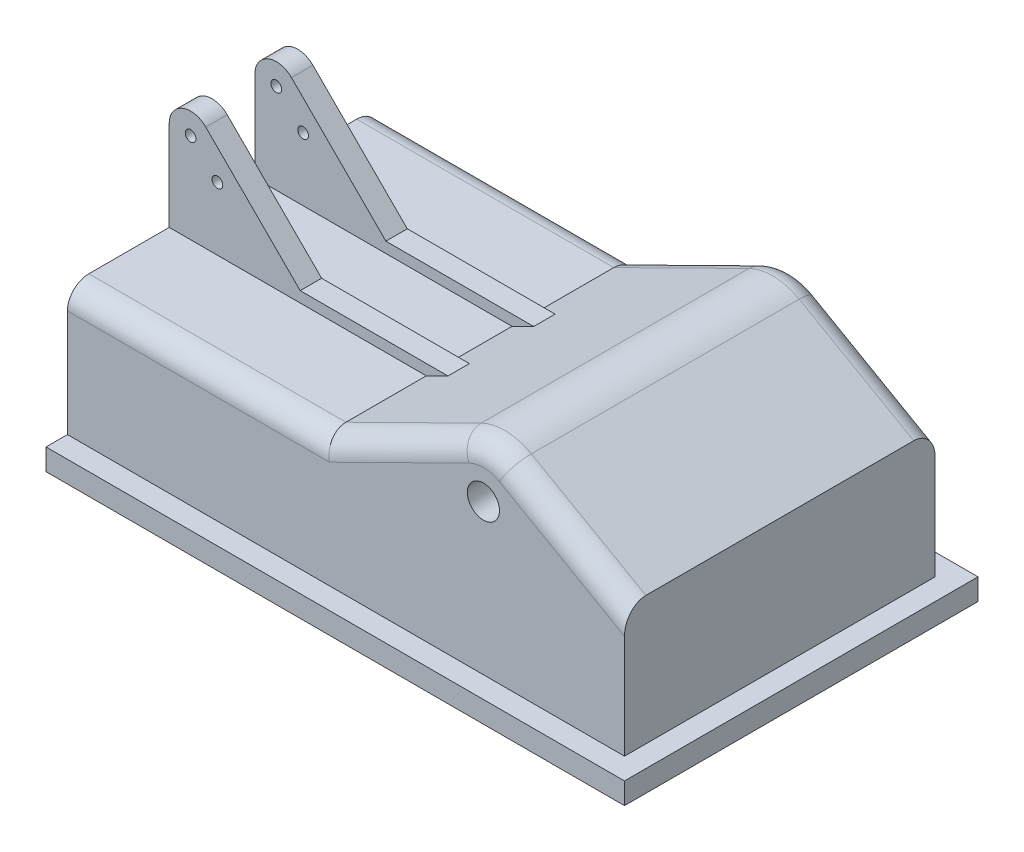
SolidWorks part; units mm, degrees
ref_plane "Front Plane" through (0, 0, 0) normal (0, 0, 1) x (1, 0, 0)
ref_plane "Top Plane" through (0, 0, 0) normal (0, 1, 0) x (1, 0, 0)
ref_plane "Right Plane" through (0, 0, 0) normal (1, 0, 0) x (0, 0, -1)
sketch "Sketch1" plane through (0, 0, 0) normal (0, 0, 1) x (1, 0, 0)
  line L0 (-260, 0) -> (260, 0)
  line L1 (-260, 0) -> (-260, 120)
  line L2 (-260, 120) -> (-20, 120)
  line L3 (-20, 120) -> (106.167, 182.3627)
  line L4 (153.0936, 180.972) -> (260, 120)
  line L5 (260, 120) -> (260, 0)
  line L6 (128.3226, 137.5393) -> (128.3226, 187.5393) construction
  arc A0 (106.167, 182.3627) -> (153.0936, 180.972) centre (128.3226, 137.5393) cw
  circle A1 centre (128.3226, 140) radius 15
  point P4 (0, 0)
  point P11 (130, 194.143)
  dimension "D7" = 50
  dimension "D8" = 30
  dimension "D1" = 520
  dimension "D2" = 120
  dimension "D3" = 120
  dimension "D4" = 130
  dimension "D5" = 150
  dimension "D6" = 124
  dimension "D9" = 140
extrude "Boss-Extrude1" add sketch "Sketch1" along normal mid plane 290
sketch "Sketch2" plane through (0, 0, 0) normal (0, 0, 1) x (1, 0, 0)
  line L0 (-260, 120) -> (-260, 204)
  line L1 (-225.8579, 218.1421) -> (-137.7157, 130)
  line L2 (-137.7157, 130) -> (0.2312, 130)
  line L3 (-240, 204) -> (-188.7568, 152.7568) construction
  line L4 (0.2312, 130) -> (-20, 120)
  line L5 (-20, 120) -> (-260, 120)
  line L6 (106.167, 182.3627) -> (-20, 120) construction
  line L7 (-20, 120) -> (-260, 120) construction
  arc A0 (-260, 204) -> (-225.8579, 218.1421) centre (-240, 204) cw
  circle A1 centre (-240, 204) radius 5
  circle A2 centre (-215, 179) radius 5
  dimension "D2" = 20
  dimension "D5" = 10
  dimension "D6" = 10
  dimension "D1" = 84
  dimension "D3" = 10
  dimension "D4" = 45
  dimension "D7" = 25
extrude "Boss-Extrude2" add sketch "Sketch2" along normal blind 20 from offset 30
mirror "Mirror1" about plane through (0, 0, 0) normal (0, 0, 1) of "Boss-Extrude2"
shell "Shell1" thickness 20 removed face at (0, 0, 0)
sketch "Sketch3" plane through (0, 0, 0) normal (0, -1, 0) x (1, 0, 0)
  line L0 (-260, 145) -> (260, 145) construction
  line L1 (-260, 165) -> (280, 165)
  line L2 (-260, 165) -> (-260, -165)
  line L3 (-260, -165) -> (280, -165)
  line L4 (280, 165) -> (280, -165)
  line L5 (260, 145) -> (260, -145) construction
  line L6 (-260, -145) -> (260, -145) construction
  line L7 (-240, -125) -> (240, -125) construction
  line L8 (240, -125) -> (160.5261, -125) construction
  line L9 (240, 125) -> (240, -125) construction
  line L10 (-240, 125) -> (240, 125) construction
  line L11 (93.3226, 125) -> (163.3226, 125) construction
  line L12 (96.9373, 125) -> (-15.327, 125) construction
  line L13 (-15.327, 125) -> (-240, 125) construction
  line L14 (-240, 125) -> (-240, -125) construction
  line L15 (-240, -125) -> (240, -125)
  line L16 (240, -125) -> (160.5261, -125)
  line L17 (240, 125) -> (240, -125)
  line L18 (-240, 125) -> (240, 125)
  line L19 (93.3226, 125) -> (163.3226, 125)
  line L20 (96.9373, 125) -> (-15.327, 125)
  line L21 (-15.327, 125) -> (-240, 125)
  line L22 (-240, 125) -> (-240, -125)
  line M5 (-260, -145) -> (260, -145)
  line M6 (260, -145) -> (260, 145)
  line M7 (260, 145) -> (-260, 145)
  line M8 (-260, 145) -> (-260, -145)
  line M9 (240, -125) -> (-240, -125)
  line M10 (-240, -125) -> (-240, 125)
  line M11 (-240, 125) -> (240, 125)
  line M12 (240, 125) -> (240, -125)
  dimension "D1" = 20
  dimension "D2" = 20
  dimension "D3" = 20
  dimension "D4" = 20
  dimension "D5" = 330
  dimension "D6" = 260
extrude "Boss-Extrude3" add sketch "Sketch3" along normal blind 20 contours L15 L18 L19 M8 M5 M6 M7 M12 M9 M10 M11 | L4 L1 L2 L3 M7 M6 M5 region at (10, 0, 158.6715) region at (0, 0, 139.046)
fillet "Fillet1" radius 20 8 edges at (43.0835, 151.1813, 145) (129.8037, 187.5174, 145) (206.5468, 150.486, -145) (129.8037, 187.5174, -145) (-140, 120, 145) (206.5468, 150.486, 145) (43.0835, 151.1813, -145) (-140, 120, -145)
